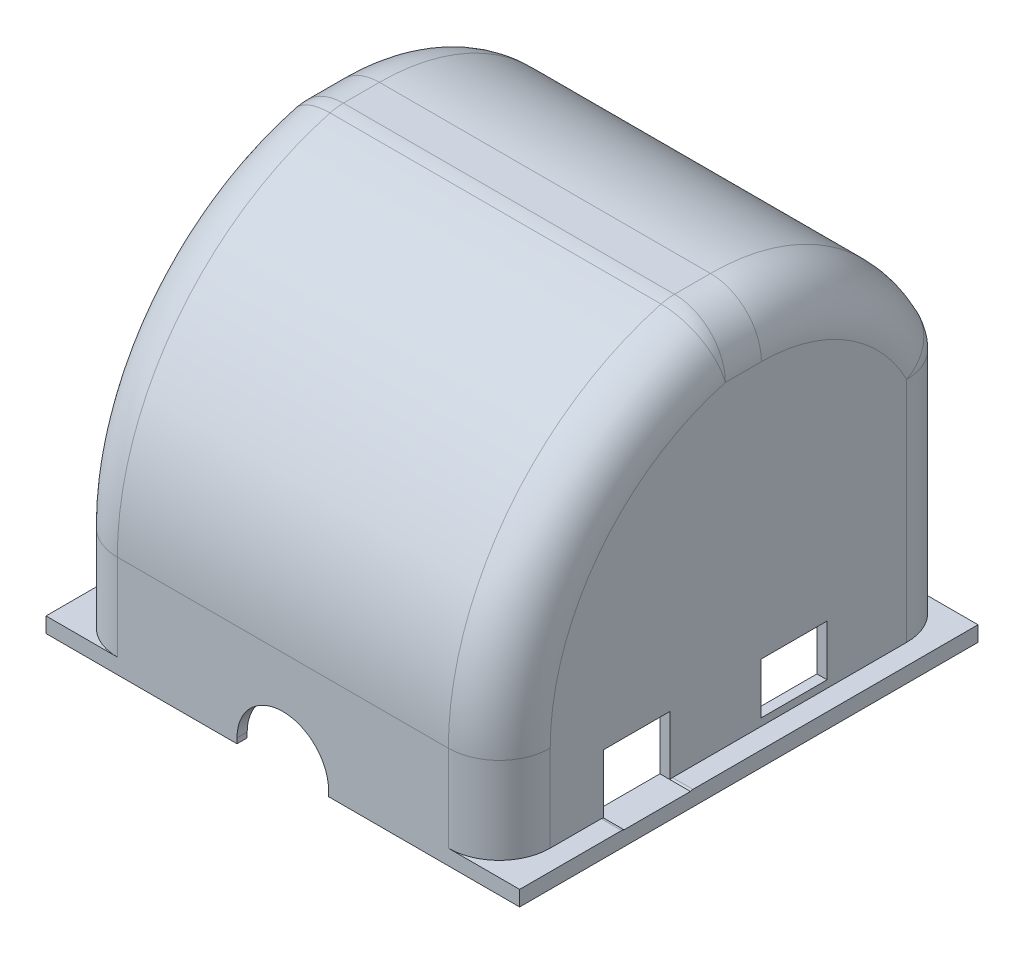
SolidWorks part; units mm, degrees
material "ABS"
ref_plane "Front Plane" through (0, 0, 0) normal (0, 0, 1) x (1, 0, 0)
ref_plane "Top Plane" through (0, 0, 0) normal (0, 1, 0) x (1, 0, 0)
ref_plane "Right Plane" through (0, 0, 0) normal (1, 0, 0) x (0, 0, -1)
sketch "Sketch1" plane through (0, 0, 0) normal (0, 1, 0) x (1, 0, 0)
  line L0 (-32.5, -45) -> (42.5, -45)
  line L1 (-32.5, -45) -> (-42.5, -45)
  line L2 (0, 0) -> (-42.5, 0) construction
  line L3 (-42.5, -45) -> (-42.5, 45)
  line L4 (-42.5, 45) -> (42.5, 45)
  line L5 (42.5, 45) -> (42.5, -45)
  point P11 (-42.5, 0)
  dimension "D1" = 75
  dimension "D2" = 10
  dimension "D3" = 42.5
  dimension "D4" = 90
extrude "Boss-Extrude1" add sketch "Sketch1" along normal blind 75
sketch "Sketch2" plane through (0, 0, 0) normal (0, 1, 0) x (1, 0, 0)
  line L0 (0, 0) -> (46.5, 0) construction
  line L1 (46.5, 20) -> (46.5, -45)
  line L2 (42.5, 45) -> (46.5, 45)
  line L3 (42.5, 45) -> (42.5, -45)
  line L4 (46.5, 20) -> (46.5, 30)
  line L5 (46.5, 45) -> (46.5, 30)
  line L6 (-46.5, -30) -> (-46.5, -20)
  line L7 (-46.5, 30) -> (-46.5, 20)
  line L8 (42.5, -45) -> (42.5, 45) construction
  line L10 (42.5, -45) -> (46.5, -45)
  line L12 (42.5, 45) -> (46.5, 45)
  line L14 (42.5, -45) -> (46.5, -45)
  line L17 (42.5, -45) -> (46.5, -45)
  line L19 (42.5, -45) -> (46.5, -45)
  line L21 (42.5, -45) -> (46.5, -45)
  line L22 (0, 0) -> (0, 45) construction
  line L23 (42.5, 45) -> (-42.5, 45) construction
  line L24 (42.5, 45) -> (46.5, 45)
  line L27 (42.5, -45) -> (46.5, -45)
  line L30 (42.5, -45) -> (46.5, -45)
  line L33 (42.5, -45) -> (46.5, -45)
  line L34 (42.5, 45) -> (46.5, 45)
  line L44 (42.5, 45) -> (46.5, 45)
  line L51 (-42.5, 45) -> (-46.5, 45)
  line L54 (42.5, 45) -> (46.5, 45)
  line L56 (-42.5, 45) -> (-46.5, 45)
  line L60 (-42.5, 45) -> (-46.5, 45)
  line L64 (42.5, 45) -> (46.5, 45)
  line L67 (-42.5, 45) -> (-46.5, 45)
  line L74 (42.5, 45) -> (46.5, 45)
  line L81 (-42.5, 45) -> (-46.5, 45)
  line L82 (-42.5, -45) -> (-46.5, -45)
  line L84 (-46.5, -45) -> (-46.5, -30)
  line L85 (-42.5, -45) -> (-46.5, -45)
  line L88 (-42.5, -45) -> (-46.5, -45)
  line L91 (-42.5, 45) -> (-46.5, 45)
  line L92 (-42.5, -45) -> (-46.5, -45)
  line L94 (-42.5, -45) -> (-46.5, -45)
  line L96 (-42.5, -45) -> (-46.5, -45)
  line L99 (-42.5, -45) -> (-46.5, -45)
  line L101 (-42.5, 45) -> (-46.5, 45)
  line L103 (-42.5, -45) -> (-46.5, -45)
  line L107 (-46.5, 45) -> (-46.5, 30)
  line L109 (-42.5, 45) -> (-42.5, -45)
  line L110 (-42.5, 45) -> (-46.5, 45)
  line L111 (-46.5, -20) -> (-46.5, 20)
  point P22 (42.5, 0)
  point P34 (-42.5, 0)
  dimension "D1" = 46.5
extrude "Boss-Extrude2" add sketch "Sketch2" along normal blind 3 contours L111 L84 L82 L109 L51 L107 | L5 L2 L3 L10 region at (44.5, 0, 0) region at (-44.5, 0, 0)
sketch "Sketch3" plane through (0, 0, 0) normal (1, 0, 0) x (0, 0, -1)
  line L0 (-45, 20) -> (-45, 0) construction
  line L1 (-45, 75) -> (-45, 3) construction
  line L2 (-45, 75) -> (45, 75) construction
  line L3 (-1.8728, 75) -> (6.472, 75)
  line L4 (45, 75) -> (45, 3) construction
  line L5 (45, 50) -> (45, 0)
  line L6 (45, 0) -> (45, 50) construction
  line L7 (-45, 20) -> (-45, 75)
  line L8 (-45, 75) -> (45, 75)
  line L9 (45, 75) -> (45, 50)
  line L10 (45, 0) -> (-45, 0) construction
  arc A0 (-45, 20) -> (-1.8728, 75) centre (11.6343, 20) cw
  arc A1 (6.472, 75) -> (45, 50) centre (6.472, 32.8119) cw
  point P0 (-51.396, -2.0763)
  dimension "D2" = 56.6343
  dimension "D4" = 42.1881
  dimension "D1" = 20
  dimension "D3" = 50
  dimension "D5" = 8.3448
extrude "Cut-Extrude1" cut sketch "Sketch3" against normal through all both and the other way through all contours L7 A0 L8 | L8 A1 L9 region at (0, 68.1333, -36.026) region at (0, 62.4722, 33.7842)
fillet "Fillet1" radius 10 12 edges at (42.5, 54.9462, 32.9325) (42.5, 11.5, 45) (-42.5, 11.5, 45) (-42.5, 54.9462, 32.9325) (0, 75, 1.8728) (42.5, 26.5, -45) (42.5, 68.2024, -29.4362) (42.5, 75, -2.2996) (-42.5, 68.2024, -29.4362) (0, 50, -45) (-42.5, 75, -2.2996) (-42.5, 26.5, -45)
shell "Shell1" thickness 2 removed face at (0, 0, 0)
sketch "Sketch5" plane through (42.5, 0, 0) normal (1, 0, 0) x (0, 0, -1)
  line L1 (-24.5, 2.88) -> (-11.46, 2.88)
  line L2 (-24.5, 2.88) -> (-24.5, 14.5)
  line L3 (-24.5, 14.5) -> (-11.46, 14.5)
  line L4 (-11.46, 2.88) -> (-11.46, 14.5)
  line L5 (-45, 3) -> (-45, 0) construction
  line L7 (6.37, 4.45) -> (19.37, 14.45) construction
  line L8 (6.37, 14.45) -> (19.37, 14.45)
  line L9 (6.37, 14.45) -> (6.37, 4.45)
  line L10 (6.37, 4.45) -> (19.37, 4.45)
  line L11 (19.37, 14.45) -> (19.37, 4.45)
  line L12 (6.37, 14.45) -> (19.37, 4.45) construction
  line L13 (45, 0) -> (-45, 0) construction
  point P7 (12.87, 9.45)
  point P14 (12.87, 9.45)
  dimension "D1" = 13.04
  dimension "D2" = 11.62
  dimension "D3" = 20.5
  dimension "D4" = 2.88
  dimension "D5" = 24.33
  dimension "D6" = 9.45
  dimension "D7" = 10
  dimension "D8" = 13
extrude "Cut-Extrude2" cut sketch "Sketch5" along normal through all and the other way up to next
fillet "Fillet6" radius 1 2 edges at (44.5, 3, 11.46) (44.5, 3, 24.5)
sketch "Sketch6" plane through (0, 0, 45) normal (0, 0, 1) x (1, 0, 0)
  line L0 (0, 0) -> (0, 1) construction
  line L1 (-46.5, 0) -> (46.5, 0) construction
  line L2 (-9, 1) -> (9, 1)
  line L3 (-9, 1) -> (-9, 0)
  line L4 (-9, 0) -> (9, 0)
  line L5 (9, 0) -> (9, 1)
  arc A0 (-9, 1) -> (9, 1) centre (0, 1) cw
  point P7 (0, 1)
  line M8 (-46.5, 0) -> (46.5, 0)
  dimension "D1" = 1
  dimension "D2" = 18
extrude "Cut-Extrude3" cut sketch "Sketch6" against normal up to next contours L0 L4 L5 L2 | L0 L2 L3 M8 | A0 L2 region at (-4.5, 0.5, 45) region at (4.5, 0.5, 45) region at (0, 4.8197, 45)
sketch "Sketch7" plane through (0, 0, -45) normal (0, 0, -1) x (-1, 0, 0)
  line L0 (-46.5, 0) -> (46.5, 0) construction
  line L1 (-3.5, 0) -> (3.5, 0)
  arc A0 (-3.5, 0) -> (3.5, 0) centre (0, 0) cw
  dimension "D1" = 7
extrude "Cut-Extrude4" cut sketch "Sketch7" against normal up to next
